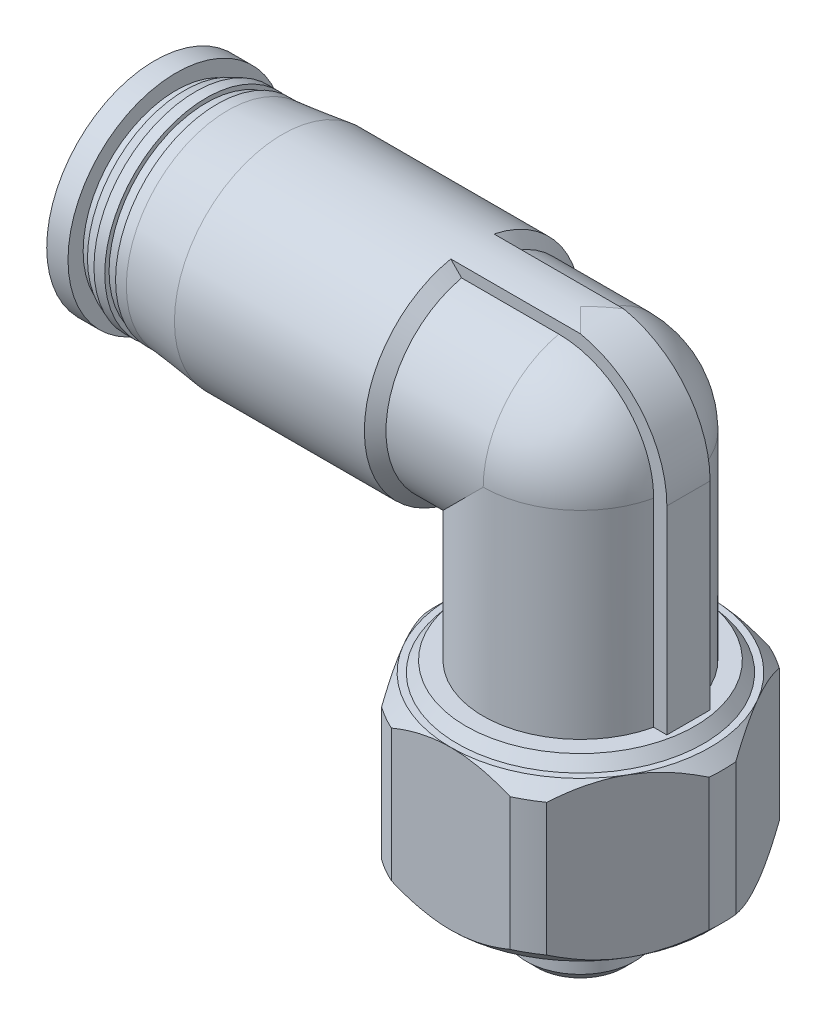
SolidWorks part; units mm, degrees
ref_plane "Front Plane" through (0, 0, 0) normal (0, 0, 1) x (1, 0, 0)
ref_plane "Top Plane" through (0, 0, 0) normal (0, 1, 0) x (1, 0, 0)
ref_plane "Right Plane" through (0, 0, 0) normal (1, 0, 0) x (0, 0, -1)
ref_plane "Plane1" through (0, 0, 0) normal (0, 0, 1) x (1, 0, 0)
sketch "Sketch1" plane through (0, 0, 0) normal (0, 0, 1) x (1, 0, 0)
  line L0 (0, 0) -> (-6, 0)
  line L1 (-6, 0) -> (-6.6, 0.6)
  line L2 (-6.6, 0.6) -> (-6.6, 6.7214)
  line L3 (-6.6, 6.7214) -> (-6, 7.3214)
  line L4 (-6, 7.3214) -> (-5.7, 7.3214)
  line L5 (-5.7, 7.3214) -> (-5.3, 7.8214)
  line L6 (-5.3, 7.8214) -> (-4.5, 7.8214)
  line L7 (-4.5, 7.8214) -> (-4.5, 17)
  line L8 (-4.5, 17) -> (0, 17)
  line L9 (0, 17) -> (0, 0)
  line L10 (0, 17) -> (0, 0) construction
revolve "Revolve1" add sketch "Sketch1" angle 360 about L10 reverse direction yes
ref_plane "Plane2" through (0, 0, 0) normal (0, 0, 1) x (1, 0, 0)
sketch "Sketch2" plane through (0, 0, 0) normal (0, 0, 1) x (1, 0, 0)
  line L0 (0, -3.5) -> (-2.0095, -3.5)
  line L1 (-2.0095, -3.5) -> (-2.5, -3.0095)
  line L2 (-2.5, -3.0095) -> (-2.5, -0.5)
  line L3 (-2.5, -0.5) -> (-3.6, -0.5)
  line L4 (-3.6, -0.5) -> (-3.6, 0)
  line L5 (-3.6, 0) -> (0, 0)
  line L6 (0, 0) -> (0, -3.5)
  line L7 (0, 0) -> (0, -3.5) construction
revolve "Revolve2" add sketch "Sketch2" angle 360 about L7 reverse direction yes
cosmetic thread "Cosmetic Thread1" parameters "D1"=3, "D2"=4.019
ref_plane "Plane3" through (0, 0, 0) normal (0, 1, 0) x (1, 0, 0)
sketch "Sketch3" plane through (0, 0, 0) normal (0, 1, 0) x (1, 0, 0)
  line L0 (-12, -12) -> (12, -12)
  line L1 (12, -12) -> (12, 12)
  line L2 (12, 12) -> (-12, 12)
  line L3 (-12, 12) -> (-12, -12)
  line L4 (-6.9282, 0) -> (-3.4641, -6)
  line L5 (-3.4641, -6) -> (3.4641, -6)
  line L6 (3.4641, -6) -> (6.9282, 0)
  line L7 (6.9282, 0) -> (3.4641, 6)
  line L8 (3.4641, 6) -> (-3.4641, 6)
  line L9 (-3.4641, 6) -> (-6.9282, 0)
extrude "Cut-Extrude1" cut sketch "Sketch3" along normal blind 8.2
ref_plane "Plane4" through (0, 0, 0) normal (0, 0, 1) x (1, 0, 0)
sketch "Sketch4" plane through (0, 0, 0) normal (0, 0, 1) x (1, 0, 0)
  line L0 (-19.7, 17) -> (-19.7, 22)
  line L1 (-19.7, 22) -> (-18.715, 22)
  line L2 (-18.715, 22) -> (-18.715, 21.3)
  line L3 (-18.715, 21.3) -> (-18.315, 21.3)
  line L4 (-18.315, 21.3) -> (-18.315, 21.5)
  line L5 (-18.315, 21.5) -> (-17.815, 21.7)
  line L6 (-17.815, 21.7) -> (-17.315, 21.7)
  line L7 (-17.315, 21.7) -> (-17.315, 21.5)
  line L8 (-17.315, 21.5) -> (-16.815, 21.5)
  line L9 (-16.815, 21.5) -> (-16.815, 21.7)
  line L10 (-16.815, 21.7) -> (-16.315, 21.7)
  line L11 (-16.315, 21.7) -> (-13.79, 22)
  line L12 (-13.79, 22) -> (-5, 22)
  line L13 (-5, 22) -> (-4.5, 21.5)
  line L14 (-4.5, 21.5) -> (0, 21.5)
  line L15 (4.5, 17) -> (-19.7, 17)
  line L16 (4.5, 17) -> (-19.7, 17) construction
  arc A0 (0, 21.5) -> (4.5, 17) centre (0, 17) cw
revolve "Revolve3" add sketch "Sketch4" angle 360 about L16 reverse direction yes
ref_plane "Plane5" through (0, 0, 0) normal (0, 0, 1) x (1, 0, 0)
sketch "Sketch5" plane through (0, 0, 0) normal (0, 0, 1) x (1, 0, 0)
  line L0 (-5, 17) -> (0, 17)
  line L1 (0, 17) -> (0, 5.7)
  line L2 (0, 5.7) -> (5, 5.7)
  line L3 (5, 5.7) -> (5, 17)
  line L4 (0, 22) -> (-5, 22)
  line L5 (-5, 22) -> (-5, 17)
  arc A0 (5, 17) -> (0, 22) centre (0, 17) ccw
extrude "Boss-Extrude1" add sketch "Sketch5" against normal blind 1 and the other way blind 1
ref_plane "Plane6" through (0, 0, 0) normal (1, 0, 0) x (0, 0, -1)
sketch "Sketch6" plane through (0, 0, 0) normal (1, 0, 0) x (0, 0, -1)
  circle A0 centre (0, 17) radius 2
extrude "Cut-Extrude2" cut sketch "Sketch6" against normal blind 19.7
ref_plane "Plane7" through (0, 0, 0) normal (0, 0, 1) x (1, 0, 0)
sketch "Sketch7" plane through (0, 0, 0) normal (0, 0, 1) x (1, 0, 0)
  line L0 (0, -3.5) -> (-1.25, -3.5)
  line L1 (-1.25, -3.5) -> (-1.25, 1)
  line L2 (-1.25, 1) -> (-2, 1)
  line L3 (-2, 1) -> (-2, 17)
  line L4 (0, 19) -> (0, -3.5)
  line L5 (0, 19) -> (0, -3.5) construction
  arc A0 (-2, 17) -> (0, 19) centre (0, 17) cw
revolve "Cut-Revolve1" cut sketch "Sketch7" angle 360 about L5 reverse direction yes
ref_plane "Plane8" through (0, 0, 0) normal (0, 0, 1) x (1, 0, 0)
sketch "Sketch8" plane through (0, 0, 0) normal (0, 0, 1) x (1, 0, 0)
  line L0 (-7, 24) -> (-7, 22)
  line L1 (-7, 22) -> (3, 22)
  line L2 (3, 22) -> (3, 24)
  line L3 (3, 24) -> (-7, 24)
  line L4 (3, 17) -> (-7, 17) construction
revolve "Cut-Revolve2" cut sketch "Sketch8" angle 30 about L4 other way angle 30 reverse direction yes
